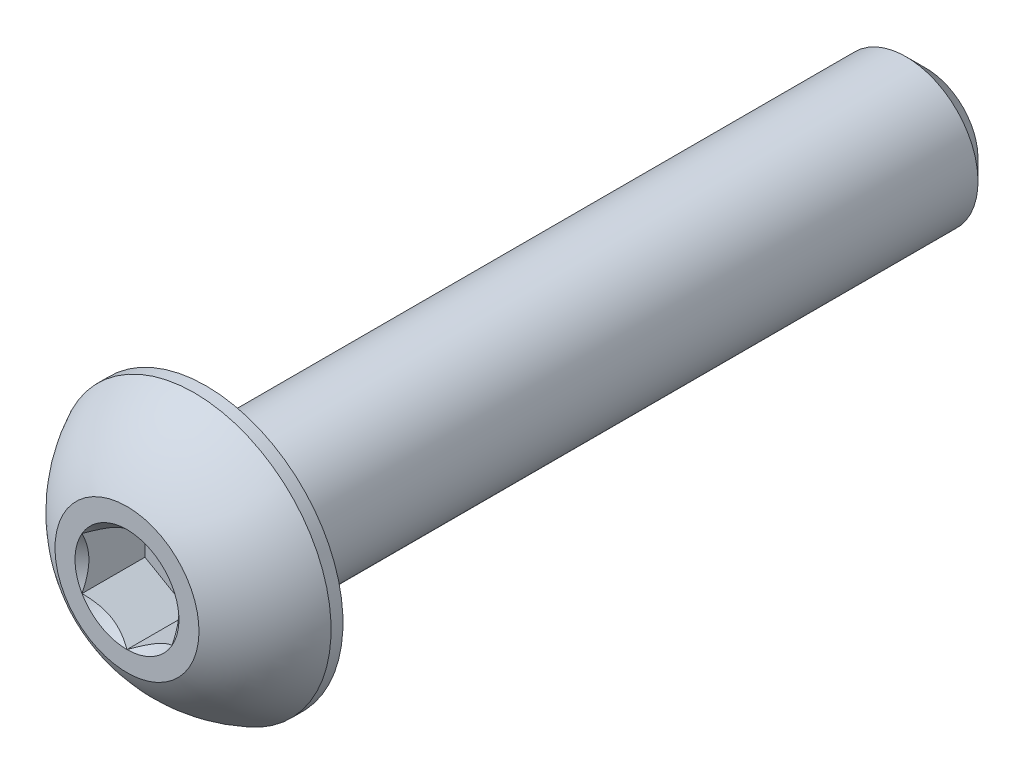
SolidWorks part; units mm, degrees
material "Alloy Steel"
ref_plane "Front Plane" through (0, 0, 0) normal (0, 0, 1) x (1, 0, 0)
ref_plane "Top Plane" through (0, 0, 0) normal (0, 1, 0) x (1, 0, 0)
ref_plane "Right Plane" through (0, 0, 0) normal (1, 0, 0) x (0, 0, -1)
sketch "Sketch1" plane through (0, 0, 0) normal (1, 0, 0) x (0, 0, -1)
  line L0 (-11.1, 0) -> (11.1, 0) construction
  line L1 (-8.9, 3.8) -> (-8.9, -3.8) construction
  line L2 (11.1, 2) -> (11.1, -2) construction
  line L3 (11.0563, 2.0758) -> (11.4063, 1.4696) construction
  line L4 (11.4063, 1.4696) -> (11.7563, 2.0758) construction
  line L5 (11.7563, 2.0758) -> (11.0563, 2.0758) construction
  line L6 (11.1, 2) -> (11.7125, 2) construction
  line L7 (11.4063, 2.0758) -> (11.4063, 2) construction
  line L8 (11.4063, 2) -> (11.4063, 1.5453) construction
  line L9 (11.4063, 1.5453) -> (11.4063, 1.4696) construction
  line L10 (11.3625, 1.5453) -> (11.45, 1.5453)
  line L11 (11.0781, 2.0379) -> (11.7344, 2.0379)
  line L12 (11.45, 1.5453) -> (11.7344, 2.0379)
  line L13 (11.3625, 1.5453) -> (11.0781, 2.0379)
  line L14 (-11.1, 1.25) -> (-11.1, -1.25) construction
  line L15 (11.1, 2) -> (-8.9, 2) construction
  point P3 (-8.9, 0)
  point P6 (-9.35, 0)
  point P21 (11.4063, 2.0379)
  point P24 (-9.23, 3.8)
  point P25 (9.35, -2)
  point P26 (-11.1, 2)
  dimension "Head Height" = 2.2
  dimension "Length" = 20
  dimension "Head Dia" = 7.6
  dimension "Thread Dia" = 4
  dimension "Pitch" = 0.7
  dimension "D2" = 0.0875
  dimension "Drive Size" = 2.5
  dimension "D1" = 1.75
  dimension "D3" = 0.33
  dimension "D4" = 1.75
sketch "Sketch2" plane through (0, 0, 0) normal (1, 0, 0) x (0, 0, -1)
  line L0 (-11.1, 0) -> (11.1, 0)
  line L1 (11.1, 0) -> (11.1, 1.44)
  line L2 (11.1, 2) -> (11.1, -2) construction
  line L3 (11.1, 1.44) -> (10.54, 2)
  line L4 (10.54, 2) -> (-8.9, 2)
  line L5 (-8.9, 3.8) -> (-8.9, -3.8) construction
  line L6 (-8.9, 2) -> (-8.9, 3.8)
  line L7 (-8.9, 3.8) -> (-9.23, 3.8)
  line L8 (11.1, 2) -> (11.7125, 2) construction
  line L9 (-11.1, 0) -> (-11.1, 2)
  arc A0 (-11.1, 2) -> (-9.23, 3.8) centre (-7.3736, 0) cw
  dimension "D1" = 0.56
  dimension "D2" = 45
revolve "Revolve1" add sketch "Sketch2" angle 360 about L0
sketch "Sketch3" plane through (0, 0, 11.1) normal (0, 0, 1) x (1, 0, 0)
  line L1 (0, 1.4434) -> (-1.25, 0.7217)
  line L2 (-1.25, 0.7217) -> (-1.25, -0.7217)
  line L3 (-1.25, -0.7217) -> (0, -1.4434)
  line L4 (0, -1.4434) -> (1.25, -0.7217)
  line L5 (1.25, -0.7217) -> (1.25, 0.7217)
  line L6 (1.25, 0.7217) -> (0, 1.4434)
  circle A0 centre (0, 0) radius 1.25 construction
  dimension "D1" = 2.5
extrude "Cut-Extrude1" cut sketch "Sketch3" against normal up to vertex (1.75 mm away) up to point (0, 0, 9.35)
sketch "Sketch4" plane through (0, 0, 11.1) normal (0, 0, 1) x (1, 0, 0)
  circle A0 centre (0, 0) radius 1.4434
extrude "Cut-Extrude2" cut sketch "Sketch4" against normal blind 10 draft 45
split "Split1" [suppressed] bodies to split 106
sketch "Sketch5" [suppressed] plane through (0, 0, -11.1) normal (0, 0, -1) x (-1, 0, 0)
  circle A0 centre (0, 0) radius 2 construction
  circle A1 centre (0, 0) radius 2
curve "Helix/Spiral1" [suppressed] pitch 0.7 height 20.7 turns 29.5714
sketch "Sketch6" [suppressed] plane through (0, 0, 0) normal (1, 0, 0) x (0, 0, -1)
  line L0 (11.3625, 1.5453) -> (11.45, 1.5453) construction
  line L1 (11.3625, 1.5453) -> (11.0781, 2.0379) construction
  line L2 (11.0781, 2.0379) -> (11.7344, 2.0379) construction
  line L3 (11.45, 1.5453) -> (11.7344, 2.0379) construction
  line L4 (11.3625, 1.5453) -> (11.45, 1.5453)
  line L5 (11.3625, 1.5453) -> (11.0781, 2.0379)
  line L6 (11.0781, 2.0379) -> (11.7344, 2.0379)
  line L7 (11.45, 1.5453) -> (11.7344, 2.0379)
sweep "Cut-Sweep1" [suppressed] cut profiles "Sketch6" path "Helix/Spiral1"
sketch "Sketch7" [suppressed] plane through (0, 0, 8.9) normal (0, 0, -1) x (-1, 0, 0)
  circle A1 centre (0, 0) radius 2
  circle A2 centre (0, 0) radius 2
  dimension "D1" = 0
extrude "Boss-Extrude1" [suppressed] add sketch "Sketch7" along normal blind 10 draft 30
equation "\"D2@Sketch1\" = \"Pitch@Sketch1\" / 8"
equation "\"D1@Sketch1\"=\"Drive Size@Sketch1\"*.7"
equation "\"D3@Sketch1\"=\"Head Height@Sketch1\"*.15"
equation "\"D1@Sketch2\"=\"Pitch@Sketch1\"*.8"
equation "\"D1@Sketch3\"=\"Drive Size@Sketch1\""
equation "\"D4@Helix/Spiral1\"=\"Pitch@Sketch1\""
equation "\"D3@Helix/Spiral1\"=\"Length@Sketch1\"+\"Pitch@Sketch1\""
equation "\"D4@Sketch1\"=\"Pitch@Sketch1\"*2.5"
